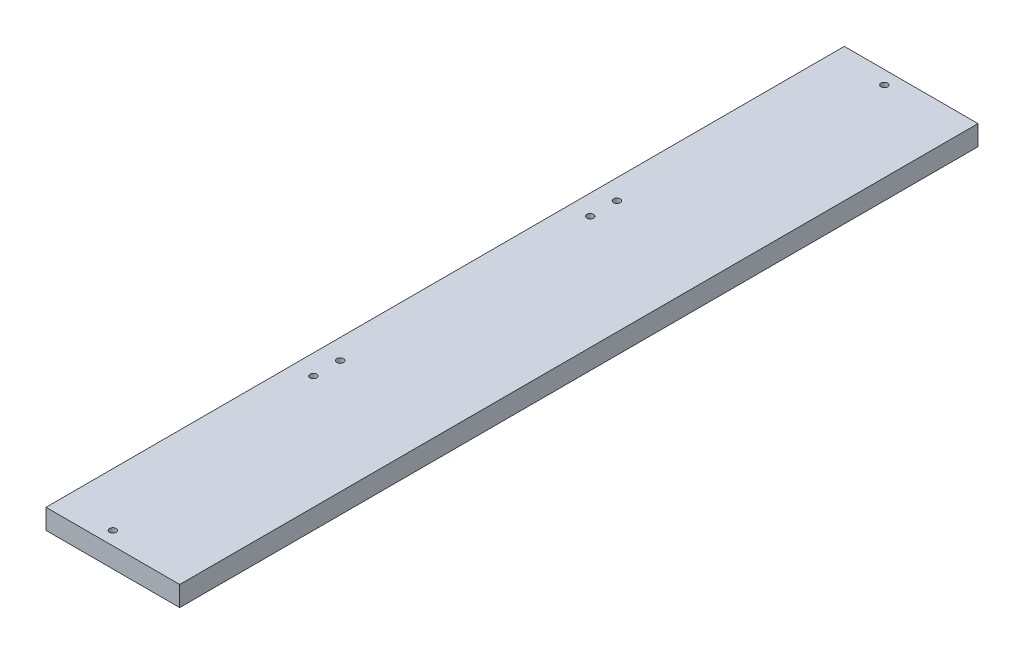
SolidWorks part; units mm, degrees
material "Pine"
ref_plane "Front Plane" through (0, 0, 0) normal (0, 0, 1) x (1, 0, 0)
ref_plane "Top Plane" through (0, 0, 0) normal (0, 1, 0) x (1, 0, 0)
ref_plane "Right Plane" through (0, 0, 0) normal (1, 0, 0) x (0, 0, -1)
sketch "Sketch1" plane through (0, 0, 0) normal (0, 1, 0) x (1, 0, 0)
  line L1 (0, 0) -> (127, 0)
  line L2 (0, 0) -> (0, -758.19)
  line L3 (0, -758.19) -> (127, -758.19)
  line L4 (127, 0) -> (127, -758.19)
  dimension "D1" = 127
  dimension "D2" = 758.19
extrude "Boss-Extrude1" add sketch "Sketch1" along normal blind 19.05
hole_wizard "1/4 (0.25) Diameter Hole1" positions "Sketch5" profile "Sketch4" hole size "1/4" standard "ANSI Inch" end condition up to next
sketch "Sketch5" plane through (0, 0, 0) normal (0, -1, 0) x (-1, 0, 0)
  point P0 (-50.8, -745.49)
  point P3 (-19.05, -523.24)
  point P6 (-19.05, -497.84)
  point P9 (-19.05, -260.35)
  point P12 (-19.05, -234.95)
  point P15 (-50.8, -12.7)
sketch "Sketch4" plane through (50.8, 0, 745.49) normal (1, 0, 0) x (0, 0, -1)
  line L0 (0, 0) -> (0, 19.05)
  line L1 (0, 19.05) -> (3.175, 19.05)
  line L2 (3.175, 19.05) -> (3.175, 0)
  line L5 (3.175, 0) -> (0, 0)
  line L11 (0, -6.35) -> (0, 107.95) construction
  dimension "Thru Hole Dia." = 6.35
  dimension "Thru Hole Depth" = 19.05
